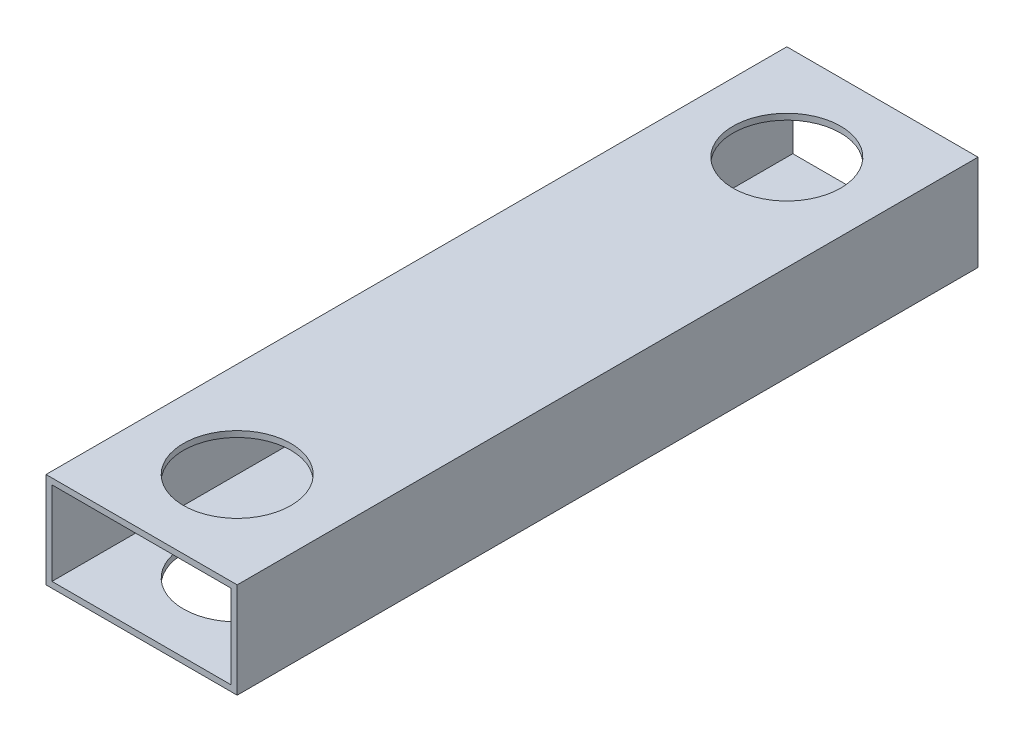
SolidWorks part; units mm, degrees
ref_plane "Front Plane" through (0, 0, 0) normal (0, 0, 1) x (1, 0, 0)
ref_plane "Top Plane" through (0, 0, 0) normal (0, 1, 0) x (1, 0, 0)
ref_plane "Right Plane" through (0, 0, 0) normal (1, 0, 0) x (0, 0, -1)
sketch "Sketch1" plane through (0, 0, 0) normal (0, 0, 1) x (1, 0, 0)
  line L0 (-23.8125, 11.1125) -> (23.8125, 11.1125)
  line L2 (-25.4, 12.7) -> (25.4, 12.7)
  line L3 (-25.4, 12.7) -> (-25.4, -12.7)
  line L4 (-25.4, -12.7) -> (25.4, -12.7)
  line L5 (25.4, 12.7) -> (25.4, -12.7)
  line L10 (23.8125, 11.1125) -> (23.8125, -11.1125)
  line L11 (-23.8125, -11.1125) -> (23.8125, -11.1125)
  line L12 (-23.8125, 11.1125) -> (-23.8125, -11.1125)
  point P12 (0, 12.7)
  point P14 (25.4, 0)
  dimension "Wall Thickness" = 1.5875
  dimension "Outside Width" = 50.8
  dimension "Outside Height" = 25.4
  dimension "Inside Height" = 22.225
  dimension "Inside Width" = 47.625
sketch "Sketch2" plane through (0, 0, 0) normal (1, 0, 0) x (0, 0, -1)
  line L0 (98.425, 0) -> (-98.425, 0)
  point P4 (0, 0)
  point P7 (-98.425, 0)
  point P10 (98.425, 0)
  dimension "Length" = 196.85
sketch "Sketch3" plane through (0, 0, 0) normal (0, 0, 1) x (1, 0, 0)
  line L21 (25.4, 12.7) -> (-25.4, 12.7)
  line L22 (25.4, -12.7) -> (25.4, 12.7)
  line L23 (-25.4, -12.7) -> (25.4, -12.7)
  line L24 (-25.4, 12.7) -> (-25.4, -12.7)
  line L25 (25.4, 12.7) -> (-25.4, 12.7)
  line L26 (25.4, -12.7) -> (25.4, 12.7)
  line L27 (-25.4, -12.7) -> (25.4, -12.7)
  line L28 (-25.4, 12.7) -> (-25.4, -12.7)
  line L29 (23.8125, 11.1125) -> (-23.8125, 11.1125)
  line L30 (23.8125, -11.1125) -> (23.8125, 11.1125)
  line L31 (-23.8125, -11.1125) -> (23.8125, -11.1125)
  line L32 (-23.8125, 11.1125) -> (-23.8125, -11.1125)
  line L33 (23.8125, 11.1125) -> (-23.8125, 11.1125)
  line L34 (23.8125, -11.1125) -> (23.8125, 11.1125)
  line L35 (-23.8125, -11.1125) -> (23.8125, -11.1125)
  line L36 (-23.8125, 11.1125) -> (-23.8125, -11.1125)
  dimension "D1" = 0
  dimension "D2" = 0
extrude "Boss-Extrude1" add sketch "Sketch3" along normal up to vertex (98.425 mm away) and the other way up to vertex (98.425 mm away) up to point (0, 0, 98.425) other way up to point (0, 0, -98.425)
sketch "Drawing Reference" plane through (0, 0, 0) normal (1, 0, 0) x (0, 0, -1)
  line L0 (-98.425, 0) -> (98.425, 0) construction
  line L1 (0, -12.7) -> (0, 12.7) construction
  line L2 (-98.425, -12.7) -> (98.425, -12.7) construction
  line L5 (-98.425, 12.7) -> (98.425, 12.7) construction
  point P7 (-61.849, 0)
  point P8 (61.849, 0)
  dimension "D1" = 36.576
sketch "Sketch4" plane through (0, -12.7, 0) normal (0, -1, 0) x (1, 0, 0)
  line L0 (-25.4, 0) -> (0, 0) construction
  line L1 (-25.4, 98.425) -> (-25.4, -98.425) construction
  line L2 (0, 0) -> (0, -73.025) construction
  line L3 (0, 0) -> (0, 73.025) construction
  circle A0 centre (0, 73.025) radius 14.2875
  circle A1 centre (0, -73.025) radius 14.2875
extrude "Cut-Extrude3" cut sketch "Sketch4" against normal through all
equation "\"D1@Drawing Reference\"=\"Outside Width@Sketch1\" * 0.72"
